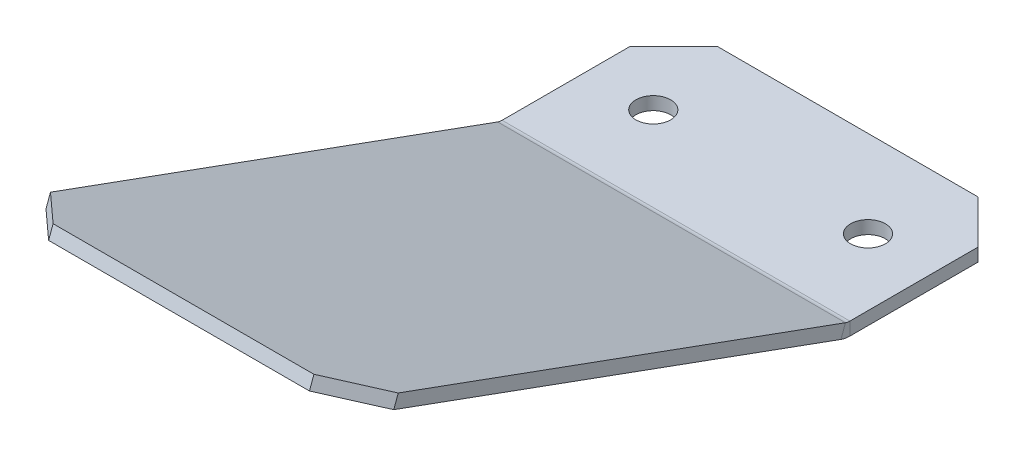
SolidWorks part; units mm, degrees
note: The reader was unsure of these and kept them because the rebuilt part matched: flange length of "Edge-Flange1".
ref_plane "Front Plane" through (0, 0, 0) normal (0, 0, 1) x (1, 0, 0)
ref_plane "Top Plane" through (0, 0, 0) normal (0, 1, 0) x (1, 0, 0)
ref_plane "Right Plane" through (0, 0, 0) normal (1, 0, 0) x (0, 0, -1)
sketch "Sketch1" plane through (0, 0, 0) normal (0, 1, 0) x (1, 0, 0)
  line L1 (-20, 10) -> (20, 10)
  line L2 (-20, 10) -> (-20, -10)
  line L3 (-20, -10) -> (20, -10)
  line L4 (20, 10) -> (20, -10)
  line L5 (-20, 10) -> (20, -10) construction
  line L6 (-20, -10) -> (20, 10) construction
  point P0 (0, 0)
  dimension "D1" = 40
  dimension "D2" = 20
sheet metal parameters "Sheet-Metal1" thickness 1.5 parameters "D1"=1.5
base flange "Base-Flange1" sketch "Sketch1" thickness 1.5 reverse thickness direction no parameters "D1"=1.5
sketch "Sketch4" plane through (0, 0, 0) normal (0, 1, 0) x (1, 0, 0)
  line L0 (-21.6851, 0) -> (22.3941, 0) construction
  line L1 (0, 11.6599) -> (0, -11.5811) construction
  circle A0 centre (-12.3493, 0) radius 2
  circle A1 centre (12.3493, 0) radius 2
  dimension "D1" = 4
extrude "Cut-Extrude1" cut sketch "Sketch4" against normal blind 10 normal cut yes
edge flange "Edge-Flange1" sketch "Sketch7" flange angle 160 flange length 60 flange position material outside bend radius 1.5 thickness 1.5 relief rectangular parameters "D6"=10
sketch "Sketch7" plane through (0, 0, 10) normal (0, -0.9397, 0.342) x (1, 0, 0)
  line L2 (-20, 0) -> (-20, 60)
  line L3 (-20, 60) -> (20, 60)
  line L4 (20, 60) -> (20, 0)
  line L5 (-20, 0) -> (20, 0) construction
  line L6 (-20, 0) -> (20, 0)
bend "EdgeBend1" bend radius 1.5 bend angle 20 parameters "D5"=1
chamfer "Chamfer1" distance 5 angle 45 4 edges at (20, 19.8164, 66.6381) (-20, 19.8164, 66.6381) (20, -0.75, -10) (-20, -0.75, -10)
flat pattern "Flat-Pattern1" [suppressed]
sketch "Bend-Lines1" plane through (0, 0, 0) normal (0, 1, 0) x (1, 0, 0)
sketch3d "Bounding-Box1" [suppressed]
  line L0 (-20, -10, 0) -> (20, -10, 0) construction
  line L1 (-20, 10, 0) -> (20, 10, 0) construction
  line L2 (-20, -10, 0) -> (-20, 10, 0) construction
  line L3 (20, -10, 0) -> (20, 10, 0) construction
bend of the flat pattern "Flatten-<EdgeBend1>1"
